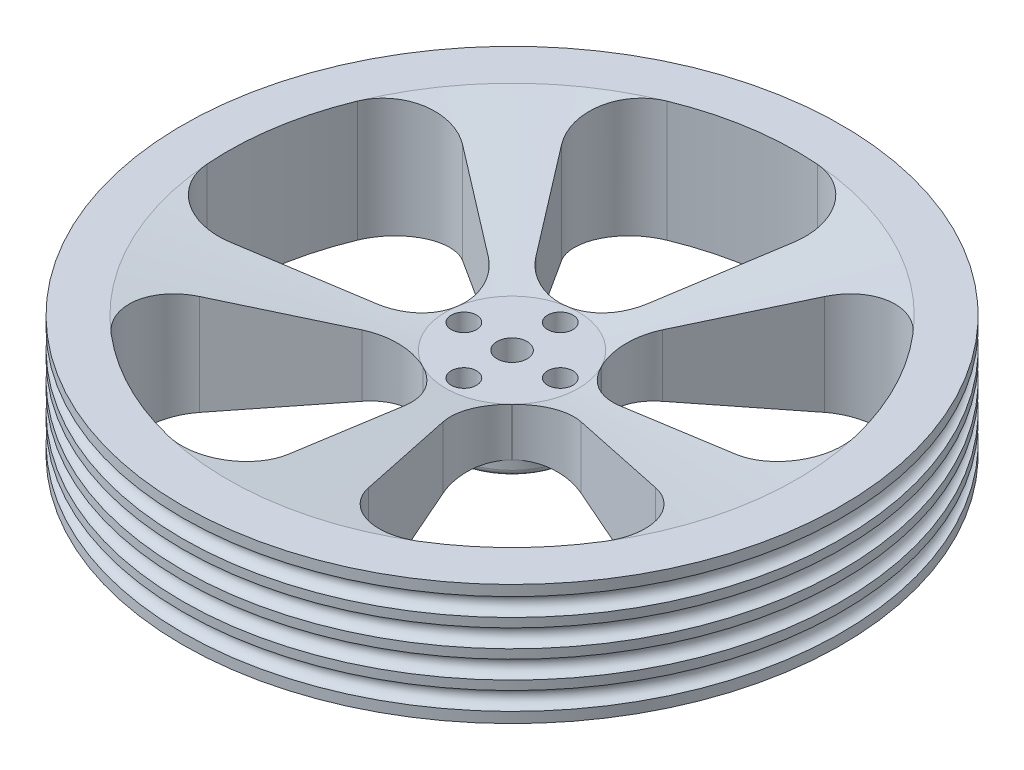
SolidWorks part; units mm, degrees
ref_plane "Спереди" through (0, 0, 0) normal (0, 0, 1) x (1, 0, 0)
ref_plane "Сверху" through (0, 0, 0) normal (0, 1, 0) x (1, 0, 0)
ref_plane "Справа" through (0, 0, 0) normal (1, 0, 0) x (0, 0, -1)
sketch "Эскиз1" plane through (0, 0, 0) normal (0, 0, 1) x (1, 0, 0)
  line L0 (0, 214.0014) -> (0, -246.251) construction
  line L1 (54.7059, 5.25) -> (54.7059, 3.75)
  line L2 (47.2059, 10) -> (54.7059, 10)
  line L3 (47.2059, 10) -> (47.2059, -10)
  line L4 (47.2059, -10) -> (54.7059, -10)
  line L5 (54.7059, 10) -> (54.7059, -10)
  line L6 (54.7059, 0.75) -> (54.7059, -0.75)
  line L7 (54.7059, -3.75) -> (54.7059, -5.25)
  line L8 (56.2059, 12.9394) -> (56.2059, -15.8407) construction
  line L10 (0, 5) -> (11, 5)
  line L11 (0, 5) -> (0, -3)
  line L12 (0, -3) -> (11, -3)
  line L13 (11, 5) -> (11, -3)
  circle A0 centre (54.7059, 6.75) radius 1.5
  circle A1 centre (54.7059, 2.25) radius 1.5
  circle A2 centre (54.7059, -2.25) radius 1.5
  circle A3 centre (54.7059, -6.75) radius 1.5
  point P7 (47.2059, 0)
  point P28 (54.7059, 0)
  dimension "D3" = 3
  dimension "D1" = 20
  dimension "D2" = 7.5
  dimension "D4" = 1.5
  dimension "D5" = 56.2059
  dimension "D6" = 11
  dimension "D7" = 5
  dimension "D8" = 8
revolve "Повернуть1" add sketch "Эскиз1" angle 360 about L0 region at (50.6319, 0, 0) region at (5.5, 1, 0)
sketch "Эскиз2" plane through (0, 0, 0) normal (0, 0, 1) x (1, 0, 0)
  line L0 (-11, -3) -> (11, -3) construction
  line L1 (-11, -3) -> (11, -3) construction
  line L2 (11, 5) -> (-11, 5) construction
  line L3 (11, 5) -> (-11, 5) construction
  line L4 (47.2059, 10) -> (-47.2059, 10) construction
  line L5 (-47.2059, -10) -> (47.2059, -10) construction
  line L6 (47.2059, 10) -> (-47.2059, 10) construction
  line L7 (-47.2059, -10) -> (47.2059, -10) construction
  line L8 (11, 5) -> (47.2059, 10)
  line L9 (11, -3) -> (47.2059, -10)
  line L10 (47.2059, -10) -> (47.2059, 10)
  line L11 (11, 5) -> (11, -3)
revolve "Повернуть2" add sketch "Эскиз2" angle 18 about L0 region at (31.6891, 0.4286, 0)
pattern_circular "Круговой массив1" count 5 over 288 about axis through (0, 214.0014, 0) along (0, -1, 0) of "Повернуть2" reverse direction yes
sketch "Эскиз3" plane through (0, 5, 0) normal (0, 1, 0) x (1, 0, 0)
  circle A0 centre (0, 0) radius 2.5
  circle A1 centre (-8, 0) radius 2.1
  circle A2 centre (0, 8) radius 2.1
  circle A3 centre (8, 0) radius 2.1
  circle A4 centre (0, -8) radius 2.1
  point P14 (0, 0)
  dimension "D1" = 5
  dimension "D2" = 4.2
  dimension "D3" = 8
  dimension "D4" = 4
extrude "Вырез-Вытянуть1" cut sketch "Эскиз3" against normal through all
fillet "Скругление1" radius 9 10 edges at (11, 1, 0) (6.4656, 1, -8.8992) (3.3992, 1, -10.4616) (-6.4656, 1, -8.8992) (-8.8992, 1, -6.4656) (-10.4616, 1, 3.3992) (-8.8992, 1, 6.4656) (0, 1, 11) (3.3992, 1, 10.4616) (10.4616, 1, 3.3992)
fillet "Скругление2" radius 9 10 edges at (-44.8955, 0, 14.5874) (-38.1904, 0, 27.7469) (0, 0, 47.2059) (14.5874, 0, 44.8955) (44.8955, 0, 14.5874) (47.2059, 0, 0) (27.7469, 0, -38.1904) (14.5874, 0, -44.8955) (-27.7469, 0, -38.1904) (-38.1904, 0, -27.7469)
sketch "Эскиз5" plane through (0, -3, 0) normal (0, -1, 0) x (1, 0, 0)
  arc A10 (9.8233, -4.95) -> (7.8129, 7.7433) centre (0, 0) ccw
  arc A11 (7.8129, 7.7433) -> (7.7433, 7.8129) centre (0, 0) ccw
  arc A12 (7.7433, 7.8129) -> (-4.95, 9.8233) centre (0, 0) ccw
  arc A13 (-4.95, 9.8233) -> (-5.0377, 9.7786) centre (0, 0) ccw
  arc A14 (-5.0377, 9.7786) -> (-10.8722, -1.6722) centre (0, 0) ccw
  arc A15 (-10.8722, -1.6722) -> (-10.8568, -1.7694) centre (0, 0) ccw
  arc A16 (-10.8568, -1.7694) -> (-1.7694, -10.8568) centre (0, 0) ccw
  arc A17 (-1.7694, -10.8568) -> (-1.6722, -10.8722) centre (0, 0) ccw
  arc A18 (-1.6722, -10.8722) -> (9.7786, -5.0377) centre (0, 0) ccw
  arc A19 (9.7786, -5.0377) -> (9.8233, -4.95) centre (0, 0) ccw
  arc A20 (9.8233, -4.95) -> (7.8129, 7.7433) centre (0, 0) ccw
  arc A21 (7.8129, 7.7433) -> (7.7433, 7.8129) centre (0, 0) ccw
  arc A22 (7.7433, 7.8129) -> (-4.95, 9.8233) centre (0, 0) ccw
  arc A23 (-4.95, 9.8233) -> (-5.0377, 9.7786) centre (0, 0) ccw
  arc A24 (-5.0377, 9.7786) -> (-10.8722, -1.6722) centre (0, 0) ccw
  arc A25 (-10.8722, -1.6722) -> (-10.8568, -1.7694) centre (0, 0) ccw
  arc A26 (-10.8568, -1.7694) -> (-1.7694, -10.8568) centre (0, 0) ccw
  arc A27 (-1.7694, -10.8568) -> (-1.6722, -10.8722) centre (0, 0) ccw
  arc A28 (-1.6722, -10.8722) -> (9.7786, -5.0377) centre (0, 0) ccw
  arc A29 (9.7786, -5.0377) -> (9.8233, -4.95) centre (0, 0) ccw
  dimension "D1" = 0
extrude "Бобышка-Вытянуть1" add sketch "Эскиз5" along normal blind 2.5 separate body
fillet "Скругление3" radius 1 1 edges at (0, -5.5, -11)
sketch "Эскиз6" plane through (0, -3, 0) normal (0, 1, 0) x (1, 0, 0)
  circle A14 centre (8, 0) radius 2.05
  circle A15 centre (0, 8) radius 2.05
  circle A16 centre (0, 8) radius 2.05
  circle A17 centre (0, -8) radius 2.05
  circle A18 centre (-8, 0) radius 2.05
  point P9 (0, 0)
  dimension "D1" = 0.05
  dimension "D2" = 4
extrude "Бобышка-Вытянуть2" add sketch "Эскиз6" along normal blind 2
sketch "Эскиз7" plane through (0, -3, 0) normal (0, 1, 0) x (1, 0, 0)
  circle A2 centre (0, 0) radius 2.75
  circle A3 centre (0, 0) radius 2.75
  dimension "D1" = 0.25
extrude "Вырез-Вытянуть2" cut sketch "Эскиз7" against normal offset from surface (1.5 mm away) 1 up to face at (0, -5.5, -10)
